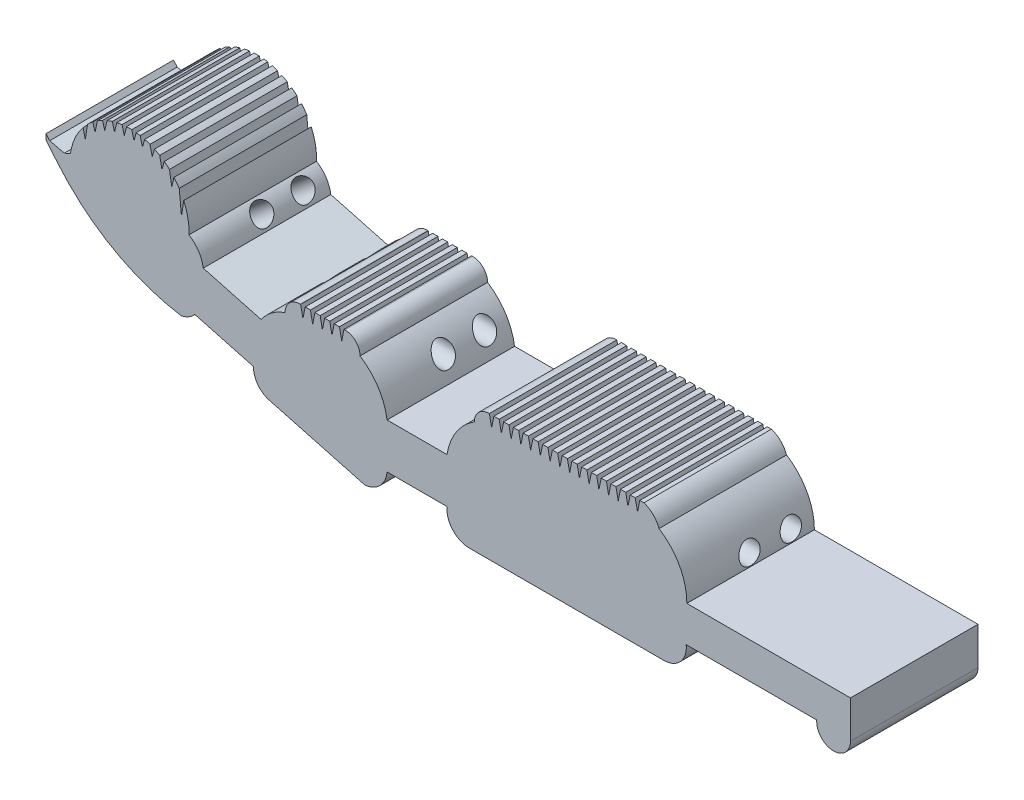
SolidWorks part; units mm, degrees
ref_plane "Front Plane" through (0, 0, 0) normal (0, 0, 1) x (1, 0, 0)
ref_plane "Top Plane" through (0, 0, 0) normal (0, 1, 0) x (1, 0, 0)
ref_plane "Right Plane" through (0, 0, 0) normal (1, 0, 0) x (0, 0, -1)
sketch "Sketch1" plane through (0, 0, 0) normal (0, 0, 1) x (1, 0, 0)
  line L3 (-37.9396, 12.057) -> (-38.2429, 13.5627)
  line L4 (-95.7349, 13.6519) -> (-97.3385, 15.5698)
  line L5 (-97.3385, 15.5698) -> (-97.3385, 16.3198)
  line L6 (-97.3385, 16.3198) -> (-96.8446, 15.7554)
  line L7 (-51.8777, 6) -> (-43.8777, 6)
  line L8 (-43.882, 0) -> (-51.882, 0)
  line L9 (-63.476, 13.5872) -> (-63.3921, 13.5872)
  line L10 (-67.3845, 0.3762) -> (-54.8288, -2.9934)
  line L11 (-19.4624, 13.557) -> (-19.7624, 12.057)
  line L12 (-19.7624, 12.057) -> (-20.0624, 13.557)
  line L13 (-20.0624, 13.557) -> (-20.7624, 13.557)
  line L14 (-94.8993, 15.2908) -> (-96.8446, 15.7554)
  line L15 (-20.7624, 13.557) -> (-21.0624, 12.057)
  line L16 (-21.0624, 12.057) -> (-21.3624, 13.557)
  line L17 (-21.3624, 13.557) -> (-22.0363, 13.557)
  line L20 (-22.0363, 13.557) -> (-22.3363, 12.057)
  line L21 (-22.3363, 12.057) -> (-22.6363, 13.557)
  line L22 (-22.6363, 13.557) -> (-23.3363, 13.557)
  line L23 (-23.3363, 13.557) -> (-23.6363, 12.057)
  line L24 (-23.6363, 12.057) -> (-23.9363, 13.557)
  line L25 (-23.9363, 13.557) -> (-24.6363, 13.557)
  line L26 (-24.6363, 13.557) -> (-24.9363, 12.057)
  line L27 (-24.9363, 12.057) -> (-25.2363, 13.557)
  line L28 (-25.2363, 13.557) -> (-25.9363, 13.557)
  line L29 (-25.9363, 13.557) -> (-26.2363, 12.057)
  line L30 (-26.2363, 12.057) -> (-26.5363, 13.557)
  line L31 (-26.5363, 13.557) -> (-27.2363, 13.557)
  line L32 (-27.2363, 13.557) -> (-27.5363, 12.057)
  line L33 (-27.5363, 12.057) -> (-27.8363, 13.557)
  line L34 (-27.8363, 13.557) -> (-28.5363, 13.557)
  line L35 (-28.5363, 13.557) -> (-28.8363, 12.057)
  line L36 (-28.8363, 12.057) -> (-29.1363, 13.557)
  line L37 (-29.1363, 13.557) -> (-29.8363, 13.557)
  line L38 (-29.8363, 13.557) -> (-30.1363, 12.057)
  line L39 (-30.1363, 12.057) -> (-30.4363, 13.557)
  line L40 (-30.4363, 13.557) -> (-31.1363, 13.557)
  line L41 (-31.1363, 13.557) -> (-31.4363, 12.057)
  line L42 (-31.4363, 12.057) -> (-31.7363, 13.557)
  line L43 (-31.7363, 13.557) -> (-32.4363, 13.557)
  line L44 (-32.4363, 13.557) -> (-32.7363, 12.057)
  line L45 (-32.7363, 12.057) -> (-33.0363, 13.557)
  line L46 (-33.0363, 13.557) -> (-33.7363, 13.557)
  line L47 (-33.7363, 13.557) -> (-34.0363, 12.057)
  line L48 (-34.0363, 12.057) -> (-34.3363, 13.557)
  line L49 (-34.3363, 13.557) -> (-35.0363, 13.557)
  line L50 (-35.0363, 13.557) -> (-35.3363, 12.057)
  line L51 (-35.3363, 12.057) -> (-35.6363, 13.557)
  line L52 (-35.6363, 13.557) -> (-36.3363, 13.557)
  line L53 (-36.3363, 13.557) -> (-36.6363, 12.057)
  line L54 (-36.6363, 12.057) -> (-36.9363, 13.557)
  line L55 (-36.9363, 13.557) -> (-37.6363, 13.557)
  line L68 (-37.6363, 13.557) -> (-37.9396, 12.057)
  line L69 (-57.476, 13.5872) -> (-57.6181, 13.5872)
  line L70 (-57.6181, 13.5872) -> (-57.9181, 12.0872)
  line L71 (-57.9181, 12.0872) -> (-58.2181, 13.5872)
  line L72 (-58.2181, 13.5872) -> (-58.9181, 13.5872)
  line L73 (-58.9181, 13.5872) -> (-59.2181, 12.0872)
  line L74 (-59.2181, 12.0872) -> (-59.5181, 13.5872)
  line L75 (-59.5181, 13.5872) -> (-60.1921, 13.5872)
  line L76 (-60.1921, 13.5872) -> (-60.4921, 12.0872)
  line L77 (-60.4921, 12.0872) -> (-60.7921, 13.5872)
  line L78 (-60.7921, 13.5872) -> (-61.4921, 13.5872)
  line L79 (-61.4921, 13.5872) -> (-61.7921, 12.0872)
  line L80 (-61.7921, 12.0872) -> (-62.0921, 13.5872)
  line L81 (-62.0921, 13.5872) -> (-62.7921, 13.5872)
  line L82 (-62.7921, 13.5872) -> (-63.0921, 12.0872)
  line L83 (-63.0921, 12.0872) -> (-63.3921, 13.5872)
  line L84 (-78.9797, 17.789) -> (-79.2797, 15.789)
  line L85 (-79.2797, 15.789) -> (-79.5797, 18.8864)
  line L86 (-80.2797, 19.8069) -> (-80.5797, 18.6069)
  line L87 (-80.5797, 18.6069) -> (-80.8797, 20.419)
  line L88 (-81.5797, 20.9917) -> (-81.8797, 19.8917)
  line L89 (-81.8797, 19.8917) -> (-82.1797, 21.3888)
  line L90 (-82.8797, 21.7627) -> (-83.1797, 20.7627)
  line L91 (-83.1797, 20.7627) -> (-83.4797, 22.0168)
  line L92 (-84.1797, 22.2444) -> (-84.4797, 21.1944)
  line L93 (-84.4797, 21.1944) -> (-84.7797, 22.385)
  line L94 (-85.3021, 22.4628) -> (-85.6021, 21.3628)
  line L95 (-85.6021, 21.3628) -> (-85.9021, 22.5027)
  line L96 (-86.6033, 22.4924) -> (-86.9033, 21.3018)
  line L97 (-86.9033, 21.3018) -> (-87.2033, 22.4348)
  line L98 (-87.9011, 22.3097) -> (-88.2011, 21.0526)
  line L99 (-88.2011, 21.0526) -> (-88.5011, 22.1501)
  line L100 (-89.2006, 21.8988) -> (-89.5006, 20.5988)
  line L101 (-89.5006, 20.5988) -> (-89.8006, 21.6219)
  line L102 (-90.4988, 21.2189) -> (-90.7988, 19.7189)
  line L103 (-90.7988, 19.7189) -> (-91.0988, 20.791)
  line L104 (-91.8003, 20.1711) -> (-92.1003, 18.2711)
  line L105 (-92.1003, 18.2711) -> (-92.4003, 19.5049)
  line L109 (-76.3772, 11.2737) -> (-68.6506, 9.2001)
  line L110 (-77.5192, 5.3678) -> (-69.6786, 3.2637)
  line L115 (-27.941, -3.3091) -> (-27.941, 1.6909) construction
  line L116 (-40.854, -3.3091) -> (-15.028, -3.3091)
  line L119 (0, 4.8) -> (-11.9164, 4.8)
  line L120 (-18.7884, 13.557) -> (-19.4624, 13.557)
  line L121 (-18.1884, 13.557) -> (-17.6348, 13.557)
  line L124 (-18.1884, 13.557) -> (-18.4884, 12.057)
  line L125 (-18.4884, 12.057) -> (-18.7884, 13.557)
  line L126 (-17.6348, 7.7582) -> (-17.6348, 13.557) construction
  line L127 (-12, 0) -> (0, 0)
  line L132 (0, 4.8) -> (5.3954, 4.8)
  line L133 (0, 4.8) -> (0, 0) construction
  line L135 (0, 2.4) -> (11.9667, 2.4) construction
  line L136 (9.8954, -0.2) -> (9.8954, 4.8)
  line L138 (9.8954, 4.8) -> (5.3954, 4.8)
  line L139 (5.3954, -0.2) -> (5.3954, 0)
  line L140 (5.3954, 0) -> (0, 0)
  line L144 (-51.8777, 6) -> (-51.882, 0) construction
  line L145 (0, 0) -> (15.2908, 0) construction
  line L146 (7.6454, 0) -> (7.6454, 8) construction
  line L147 (7.6454, -4) -> (7.6454, 0) construction
  line L148 (15.2908, 8) -> (15.2908, 0) construction
  line L149 (0, 8) -> (15.2908, 8) construction
  line L150 (-43.8777, 6) -> (-43.882, 0) construction
  line L151 (7.6454, -7) -> (7.6454, -4) construction
  line L153 (5.3954, 4.8) -> (5.3954, 5) construction
  arc A0 (-95.7349, 13.6519) -> (-79.3346, 4.3072) centre (-74.9884, 30.9988) ccw
  arc A1 (-38.2429, 13.5627) -> (-39.7687, 12.8796) centre (-38.2663, 11.5694) ccw
  arc A2 (-40.253, 11.5872) -> (-43.8777, 6) centre (-35.9825, 4.8474) ccw
  arc A3 (-39.7687, 12.8796) -> (-40.253, 11.5872) centre (-38.2866, 11.5872) ccw
  arc A4 (-78.2797, 14.1613) -> (-78.9797, 17.789) centre (-86.3128, 14.4926) ccw
  arc A5 (-79.5797, 18.8864) -> (-80.2797, 19.8069) centre (-86.3128, 14.4926) ccw
  arc A6 (-80.8797, 20.419) -> (-81.5797, 20.9917) centre (-86.3128, 14.4926) ccw
  arc A7 (-43.882, 0) -> (-40.854, -3.3091) centre (-40.898, -0.3094) ccw
  arc A8 (-82.1797, 21.3888) -> (-82.8797, 21.7627) centre (-86.3128, 14.4926) ccw
  arc A9 (-54.8288, -2.9934) -> (-51.882, 0) centre (-55.1408, 0.261) ccw
  arc A10 (-69.6786, 3.2637) -> (-67.3845, 0.3762) centre (-66.8053, 3.1914) ccw
  arc A12 (-83.4797, 22.0168) -> (-84.1797, 22.2444) centre (-86.3128, 14.4926) ccw
  arc A13 (-84.7797, 22.385) -> (-85.3021, 22.4628) centre (-85.9238, 16.4951) ccw
  arc A15 (-85.9021, 22.5027) -> (-86.6033, 22.4924) centre (-86.1352, 14.4662) ccw
  arc A16 (-79.3346, 4.3072) -> (-77.5192, 5.3678) centre (-79.8443, 7.2636) ccw
  arc A17 (-76.3772, 11.2737) -> (-78.2797, 14.1613) centre (-80.3785, 10.708) ccw
  arc A18 (-65.476, 11.5872) -> (-68.6506, 9.2001) centre (-63.5743, 5.7536) ccw
  arc A19 (-51.8777, 6) -> (-55.476, 11.5872) centre (-59.7756, 4.8659) ccw
  arc A20 (-55.476, 11.5872) -> (-57.476, 13.5872) centre (-57.476, 11.5872) ccw
  arc A21 (-63.476, 13.5872) -> (-65.476, 11.5872) centre (-63.476, 11.5872) ccw
  arc A22 (-94.0899, 15.6336) -> (-94.8993, 15.2908) centre (-87.5738, -0.8806) ccw
  arc A24 (-87.2033, 22.4348) -> (-87.9011, 22.3097) centre (-86.1352, 14.4662) ccw
  arc A26 (-88.5011, 22.1501) -> (-89.2006, 21.8988) centre (-86.1352, 14.4662) ccw
  arc A27 (-89.8006, 21.6219) -> (-90.4988, 21.2189) centre (-86.1352, 14.4662) ccw
  arc A30 (-91.0988, 20.791) -> (-91.8003, 20.1711) centre (-86.1352, 14.4662) ccw
  arc A38 (-92.4003, 19.5049) -> (-94.0899, 15.6336) centre (-86.1352, 14.4662) ccw
  arc A40 (-12, 0) -> (-15.028, -3.3091) centre (-14.984, -0.3094) cw
  arc A41 (-15.6247, 11.5872) -> (-17.6348, 13.557) centre (-18.6728, 10.4872) ccw
  arc A42 (-15.6247, 11.5872) -> (-11.9164, 4.8) centre (-19.8952, 4.8474) cw
  arc A46 (5.3954, 5) -> (9.8954, 5) centre (7.6454, 5) cw construction
  arc A47 (5.3954, -0.2) -> (9.8954, -0.2) centre (7.6454, -0.2) ccw
  point P86 (-29.6483, 15.1731)
  dimension "D7" = 2
  dimension "D3" = 6
  dimension "D4" = 6
  dimension "D5" = 2.5
  dimension "D6" = 43.882
  dimension "D8" = 8
  dimension "D9" = 8
  dimension "D10" = 18.0933
  dimension "D11" = 20.0133
  dimension "D12" = 0.75
  dimension "D13" = 3.6247
  dimension "D14" = 5
  dimension "D15" = 5.6348
  dimension "D16" = 0.75
  dimension "D17" = 4.8
  dimension "D19" = 12
  dimension "D20" = 11.9164
  dimension "D21" = 8
  dimension "D22" = 8.1181
extrude "Boss-Extrude1" add sketch "Sketch1" along normal blind 17
ref_plane "Plane1" through (-60, 0, 0) normal (1, 0, 0) x (0, 0, -1)
sketch "Sketch2" plane through (-60, 0, 0) normal (1, 0, 0) x (0, 0, -1)
  line L0 (-17, 6) -> (0, 6) construction
  line L1 (0, 6) -> (0, 11.5872) construction
  line L2 (-17, 6) -> (-17, 11.5872) construction
  line L3 (-17, 11.5872) -> (0, 11.5872) construction
  line L4 (-17, 8.7936) -> (0, 8.7936) construction
  line L5 (-8.5, 11.5872) -> (-8.5, 6) construction
  circle A0 centre (-14, 8.7936) radius 1.4 construction
  circle A2 centre (-3, 8.7936) radius 1.4
  circle A3 centre (-8.5, 8.7936) radius 1.4
  dimension "D1" = 2.8
  dimension "D2" = 3
extrude "Cut-Extrude1" cut sketch "Sketch2" against normal blind 5 and the other way blind 20
sketch "Sketch3" plane through (0, 0, 0) normal (1, 0, 0) x (0, 0, -1)
  line L0 (-17, 4.8) -> (0, 4.8) construction
  line L1 (-14, 4.8) -> (-14, 6.3) construction
  line L2 (-8.5, 4.8) -> (-8.5, 11.5872) construction
  line L3 (-17, 11.5872) -> (0, 11.5872) construction
  line L4 (-17, 4.8) -> (-17, 11.5872) construction
  circle A0 centre (-14, 6.3) radius 1.4 construction
  circle A2 centre (-3, 6.3) radius 1.4
  circle A3 centre (-8.5, 6.3) radius 1.4
  dimension "D2" = 2.8
  dimension "D1" = 1.5
  dimension "D3" = 3
extrude "Cut-Extrude2" cut sketch "Sketch3" against normal blind 42
ref_plane "Plane2" through (-63.5625, 23.1628, 0) normal (0.9396, -0.3424, 0) x (0, 0, -1)
sketch "Sketch4" plane through (-63.5625, 23.1628, 0) normal (0.9396, -0.3424, 0) x (0, 0, -1)
  line L0 (-8.5, -11.5311) -> (-8.5, -14.8609) construction
  line L1 (0, -13.196) -> (-17, -13.196) construction
  line L5 (0, -14.8609) -> (-17, -14.8609) construction
  line L6 (-17, -14.8609) -> (-17, -11.5311) construction
  line L7 (-17, -11.5311) -> (0, -11.5311) construction
  line L8 (0, -11.5311) -> (0, -14.8609) construction
  circle A0 centre (-3, -13.196) radius 1.4
  circle A2 centre (-14, -13.196) radius 1.4 construction
  circle A3 centre (-8.5, -13.196) radius 1.4
  dimension "D1" = 2.8
  dimension "D2" = 3
extrude "Cut-Extrude3" cut sketch "Sketch4" along normal blind 4
ref_plane "Plane3" through (-39.2988, -32.9496, 0) normal (0.7663, 0.6425, 0) x (0, 0, -1)
sketch "Sketch5" plane through (-39.2988, -32.9496, 0) normal (0.7663, 0.6425, 0) x (0, 0, -1)
  line L0 (-17, 61.1457) -> (0, 61.1457) construction
  line L1 (0, 61.1457) -> (0, 57.7105) construction
  line L2 (-17, 57.7105) -> (0, 57.7105) construction
  line L3 (0, 57.7105) -> (0, 61.1457) construction
  line L4 (0, 57.7105) -> (-17, 57.7105) construction
  line L5 (-17, 57.7105) -> (-17, 61.1457) construction
  line L6 (-17, 59.4281) -> (0, 59.4281) construction
  line L7 (-8.5, 61.1457) -> (-8.5, 57.7105) construction
  circle A0 centre (-14, 59.4281) radius 1.4 construction
  circle A1 centre (-3, 59.4281) radius 1.4
  circle A2 centre (-8.5, 59.4281) radius 1.4
  dimension "D1" = 2.8
  dimension "D2" = 3
extrude "Cut-Extrude4" cut sketch "Sketch5" against normal blind 12 and the other way blind 12
